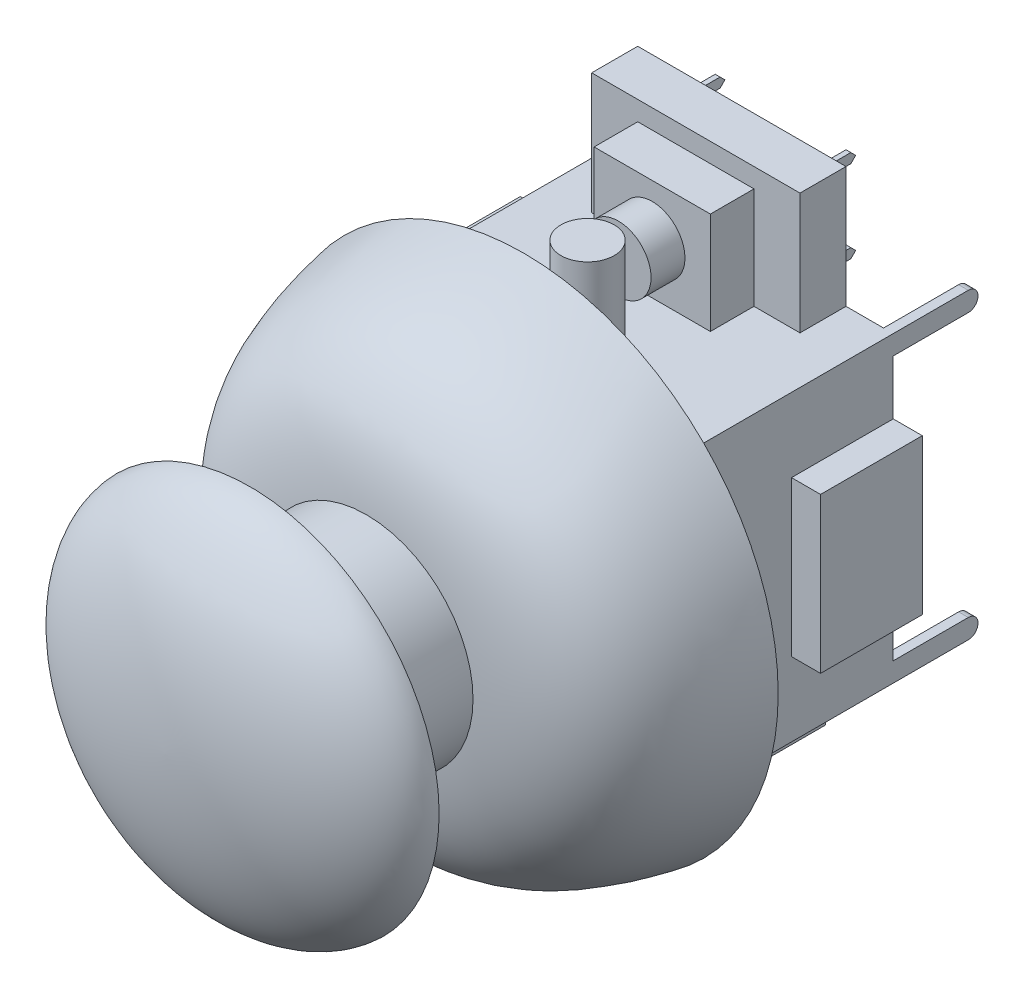
SolidWorks part; units mm, degrees
ref_plane "Front Plane" through (0, 0, 0) normal (0, 0, 1) x (1, 0, 0)
ref_plane "Top Plane" through (0, 0, 0) normal (0, 1, 0) x (1, 0, 0)
ref_plane "Right Plane" through (0, 0, 0) normal (1, 0, 0) x (0, 0, -1)
sketch "Sketch1" plane through (0, 0, 0) normal (0, 0, 1) x (1, 0, 0)
  line L1 (0, 0) -> (15.875, 0)
  line L2 (0, 0) -> (0, 15.875)
  line L3 (0, 15.875) -> (15.875, 15.875)
  line L4 (15.875, 0) -> (15.875, 15.875)
  dimension "D1" = 15.875
extrude "Boss-Extrude1" add sketch "Sketch1" along normal blind 11.938
sketch "Sketch2" plane through (0, 0, 0) normal (0, 0, -1) x (-1, 0, 0)
  line L0 (-7.9375, 15.875) -> (-7.9375, 24.013) construction
  line L1 (-15.875, 15.875) -> (0, 15.875) construction
  line L3 (-13.3985, 15.875) -> (-2.4765, 15.875)
  line L4 (-13.3985, 15.875) -> (-13.3985, 22.225)
  line L5 (-13.3985, 22.225) -> (-2.4765, 22.225)
  line L6 (-2.4765, 15.875) -> (-2.4765, 22.225)
  point P8 (-7.9375, 22.225)
  dimension "D1" = 10.922
  dimension "D2" = 6.35
extrude "Boss-Extrude2" add sketch "Sketch2" against normal blind 2.413
sketch "Sketch3" plane through (15.875, 0, 0) normal (1, 0, 0) x (0, 0, -1)
  line L0 (0, 0) -> (0, 15.875) construction
  line L1 (0, 3.8735) -> (-5.334, 3.8735)
  line L2 (0, 3.8735) -> (0, 12.0015)
  line L3 (0, 12.0015) -> (-5.334, 12.0015)
  line L4 (-5.334, 3.8735) -> (-5.334, 12.0015)
  line L5 (-11.938, 7.9375) -> (0, 7.9375) construction
  line L6 (-11.938, 0) -> (-11.938, 15.875) construction
  point P10 (-5.334, 7.9375)
  dimension "D1" = 8.128
  dimension "D2" = 5.334
extrude "Boss-Extrude3" add sketch "Sketch3" along normal blind 1.524
sketch "Sketch4" plane through (0, 0, 2.413) normal (0, 0, 1) x (1, 0, 0)
  line L0 (7.9375, 22.225) -> (7.9375, 15.875) construction
  line L1 (2.4765, 22.225) -> (13.3985, 22.225) construction
  line L2 (13.3985, 15.875) -> (2.4765, 15.875) construction
  line L3 (15.875, 15.875) -> (0, 15.875) construction
  line L4 (4.8895, 15.875) -> (10.9855, 15.875)
  line L5 (4.8895, 15.875) -> (4.8895, 21.209)
  line L6 (4.8895, 21.209) -> (10.9855, 21.209)
  line L7 (10.9855, 15.875) -> (10.9855, 21.209)
  point P12 (7.9375, 21.209)
  dimension "D1" = 6.096
  dimension "D2" = 5.334
extrude "Boss-Extrude4" add sketch "Sketch4" along normal blind 2.286
sketch "Sketch5" plane through (0, 0, 4.699) normal (0, 0, 1) x (1, 0, 0)
  line L0 (7.9375, 21.209) -> (7.9375, 15.875) construction
  line L1 (10.9855, 21.209) -> (4.8895, 21.209) construction
  line L2 (4.8895, 15.875) -> (10.9855, 15.875) construction
  line L3 (4.8895, 18.542) -> (10.9855, 18.542) construction
  line L4 (4.8895, 21.209) -> (4.8895, 15.875) construction
  line L5 (10.9855, 15.875) -> (10.9855, 21.209) construction
  circle A0 centre (7.9375, 18.542) radius 1.7145
  dimension "D1" = 3.429
extrude "Boss-Extrude5" add sketch "Sketch5" along normal blind 1.778
sketch "Sketch6" plane through (0, 15.875, 0) normal (0, 1, 0) x (1, 0, 0)
  line L0 (7.9375, -11.938) -> (7.9375, -4.699) construction
  line L1 (15.875, -11.938) -> (0, -11.938) construction
  line L2 (10.9855, -4.699) -> (4.8895, -4.699) construction
  circle A0 centre (7.9375, -8.0902) radius 1.397
  dimension "D1" = 2.794
extrude "Boss-Extrude6" add sketch "Sketch6" along normal blind 4.318
sketch "Sketch7" plane through (0, 0, 0) normal (0, -1, 0) x (1, 0, 0)
  line L0 (7.9375, 11.938) -> (7.9375, 0) construction
  line L1 (0, 11.938) -> (15.875, 11.938) construction
  line L2 (0, 0) -> (15.875, 0) construction
  line L4 (3.048, 11.938) -> (12.827, 11.938)
  line L5 (3.048, 11.938) -> (3.048, 0.508)
  line L6 (3.048, 0.508) -> (12.827, 0.508)
  line L7 (12.827, 11.938) -> (12.827, 0.508)
  point P10 (7.9375, 0.508)
  dimension "D1" = 9.779
  dimension "D2" = 11.43
extrude "Boss-Extrude7" add sketch "Sketch7" along normal blind 3.175 separate body
sketch "Sketch8" plane through (0, 0, 0) normal (-1, 0, 0) x (0, 0, 1)
  line L0 (11.938, 7.9375) -> (0, 7.9375) construction
  line L1 (11.938, 15.875) -> (11.938, 0) construction
  line L2 (0, 15.875) -> (0, 0) construction
  line L4 (11.938, 12.827) -> (0.508, 12.827)
  line L5 (11.938, 12.827) -> (11.938, 3.048)
  line L6 (11.938, 3.048) -> (0.508, 3.048)
  line L7 (0.508, 12.827) -> (0.508, 3.048)
  point P10 (0.508, 7.9375)
  dimension "D1" = 9.779
  dimension "D2" = 11.43
extrude "Boss-Extrude8" add sketch "Sketch8" along normal blind 3.175 separate body
sketch "Sketch9" plane through (-3.175, 0, 0) normal (-1, 0, 0) x (0, 0, 1)
  line L0 (11.938, 7.9375) -> (0.508, 7.9375) construction
  line L1 (11.938, 3.048) -> (11.938, 12.827) construction
  line L2 (0.508, 12.827) -> (0.508, 3.048) construction
  line L3 (7.62, 12.4456) -> (7.62, 10.8887)
  line L4 (6.096, 12.4456) -> (6.096, 10.8887)
  line L5 (11.3661, 7.1755) -> (9.8092, 7.1755)
  line L6 (11.3661, 8.6995) -> (9.8092, 8.6995)
  line L7 (6.096, 3.4294) -> (6.096, 4.9863)
  line L8 (7.62, 3.4294) -> (7.62, 4.9863)
  line L10 (2.3499, 7.1755) -> (3.9068, 7.1755)
  line L14 (2.3499, 8.6995) -> (3.9068, 8.6995)
  arc A0 (2.3499, 7.1755) -> (6.096, 3.4294) centre (6.858, 7.9375) ccw
  arc A1 (3.9068, 7.1755) -> (6.096, 4.9863) centre (6.858, 7.9375) ccw
  circle A2 centre (6.858, 7.9375) radius 2.413
  circle A3 centre (6.858, 7.9375) radius 1.8415
  arc A4 (6.096, 12.4456) -> (2.3499, 8.6995) centre (6.858, 7.9375) ccw
  arc A5 (6.096, 10.8887) -> (3.9068, 8.6995) centre (6.858, 7.9375) ccw
  arc A6 (9.8092, 8.6995) -> (7.62, 10.8887) centre (6.858, 7.9375) ccw
  arc A7 (11.3661, 8.6995) -> (7.62, 12.4456) centre (6.858, 7.9375) ccw
  arc A8 (7.62, 4.9863) -> (9.8092, 7.1755) centre (6.858, 7.9375) ccw
  arc A9 (7.62, 3.4294) -> (11.3661, 7.1755) centre (6.858, 7.9375) ccw
  point P25 (6.858, 7.9375)
  dimension "D2" = 9.144
  dimension "D3" = 6.096
  dimension "D4" = 4.826
  dimension "D5" = 3.683
  dimension "D1" = 5.08
  dimension "D8" = 1.524
  dimension "D6" = 4
extrude "Cut-Extrude1" cut sketch "Sketch9" against normal blind 0.508
sketch "Sketch10" plane through (0, -3.175, 0) normal (0, -1, 0) x (1, 0, 0)
  line L0 (7.9375, 11.938) -> (7.9375, 0.508) construction
  line L1 (3.4294, 7.62) -> (4.9863, 7.62)
  line L2 (3.4294, 6.096) -> (4.9863, 6.096)
  line L3 (8.6995, 11.3661) -> (8.6995, 9.8092)
  line L4 (7.1755, 11.3661) -> (7.1755, 9.8092)
  line L5 (12.4456, 6.096) -> (10.8887, 6.096)
  line L6 (12.4456, 7.62) -> (10.8887, 7.62)
  line L7 (8.6995, 2.3499) -> (8.6995, 3.9068)
  line L8 (7.1755, 2.3499) -> (7.1755, 3.9068)
  line L9 (3.048, 11.938) -> (12.827, 11.938) construction
  arc A0 (8.6995, 2.3499) -> (12.4456, 6.096) centre (7.9375, 6.858) ccw
  arc A1 (8.6995, 3.9068) -> (10.8887, 6.096) centre (7.9375, 6.858) ccw
  circle A2 centre (7.9375, 6.858) radius 2.413
  circle A3 centre (7.9375, 6.858) radius 1.8415
  arc A4 (3.4294, 6.096) -> (7.1755, 2.3499) centre (7.9375, 6.858) ccw
  arc A5 (4.9863, 6.096) -> (7.1755, 3.9068) centre (7.9375, 6.858) ccw
  arc A6 (7.1755, 9.8092) -> (4.9863, 7.62) centre (7.9375, 6.858) ccw
  arc A7 (7.1755, 11.3661) -> (3.4294, 7.62) centre (7.9375, 6.858) ccw
  arc A8 (10.8887, 7.62) -> (8.6995, 9.8092) centre (7.9375, 6.858) ccw
  arc A9 (12.4456, 7.62) -> (8.6995, 11.3661) centre (7.9375, 6.858) ccw
  point P18 (7.9375, 6.858)
  dimension "D1" = 4.826
extrude "Cut-Extrude2" cut sketch "Sketch10" against normal blind 0.508
ref_plane "Plane3" through (7.9375, 7.9375, 0) normal (-0.7071, -0.7071, 0) x (-0.7071, 0.7071, 0)
ref_plane "Plane4" through (0, 0, 0) normal (0.7071, -0.7071, 0) x (-0.7071, -0.7071, 0)
ref_axis "Axis2" through (7.9375, 7.9375, -0.5969) along (0, 0, 1)
sketch "Sketch11" plane through (7.9375, 7.9375, 0) normal (-0.7071, -0.7071, 0) x (-0.7071, 0.7071, 0)
  line L0 (0, -11.938) -> (0, -30.226)
  line L1 (0, 6.5659) -> (0, -6.5659) construction
  line L2 (11.2253, -11.938) -> (0, -11.938) construction
  line L3 (-18.1706, -11.43) -> (26.2656, -11.43) construction
  line L4 (11.2253, 0) -> (0, 0) construction
  line L5 (13.335, -11.43) -> (13.335, -19.685) construction
  line L6 (13.335, -19.685) -> (0, -19.685) construction
  line L7 (3.1115, -11.938) -> (3.1115, -15.1787)
  line L8 (5.588, -19.685) -> (5.588, -24.511)
  line L9 (3.1115, -15.1787) -> (5.08, -19.2254)
  line L10 (5.08, -19.2254) -> (5.08, -24.511) construction
  line L11 (13.335, -11.43) -> (12.8178, -11.43)
  line L12 (0, -30.226) -> (9.906, -30.226) construction
  line L13 (9.906, -24.511) -> (9.906, -25.781) construction
  line L14 (9.906, -24.511) -> (5.588, -24.511) construction
  line L15 (5.588, -24.511) -> (9.906, -25.781)
  line L16 (3.1115, -11.938) -> (0, -11.938)
  spline S0 degree 3 poles (5.588, -19.685) (10.7036, -19.1717) (12.3371, -16.6782) (13.335, -11.43) knots 0 0 0 0 1 1 1 1
  spline S1 degree 1 poles (5.08, -19.2254) (12.8359, -11.3351) knots 0 0 1 1 construction
  spline S2 degree 3 poles (5.08, -19.2254) (5.3999, -19.1933) (6.0617, -19.1294) (7.2028, -18.9354) (8.4381, -18.5762) (9.6141, -17.9582) (10.5555, -17.1454) (11.3172, -16.1066) (11.9356, -14.8112) (12.3533, -13.4974) (12.64, -12.3157) (12.7747, -11.6573) (12.8359, -11.3351) knots -0.029797 -0.029797 -0.029797 -0.029797 0.034566 0.098928 0.227653 0.356377 0.485102 0.613826 0.742551 0.871275 0.935638 1 1 1 1 only from (5.08, -19.2254) to (12.8178, -11.43)
  spline S3 degree 3 poles (9.906, -25.781) (9.7517, -27.8565) (6.0405, -30.162) (0, -30.226) knots 0 0 0 0 1 1 1 1
  dimension "D1" = 11.43
  dimension "D2" = 13.335
  dimension "D3" = 18.796
  dimension "D4" = 8.255
  dimension "D5" = 3.1115
  dimension "D6" = 5.588
  dimension "D7" = 4.826
  dimension "D9" = 9.906
  dimension "D10" = 1.27
  dimension "D8" = 0.508
revolve "Revolve1" add sketch "Sketch11" angle 360 about axis through (7.9375, 7.9375, -0.5969) along (0, 0, 1)
sketch "Sketch12" plane through (0, 0, 0) normal (0, -1, 0) x (1, 0, 0)
  line L0 (0, 0) -> (0, -4.445)
  line L1 (15.875, 11.938) -> (15.875, 0) construction
  line L2 (0, 0) -> (15.875, 0) construction
  line L3 (15.367, 0) -> (15.367, -4.445)
  dimension "D1" = 4.445
  dimension "D2" = 0.508
extrude "Extrude-Thin1" add sketch "Sketch12" against normal blind 1.016 thin thin type one direction reverse wall 0.508
sketch "Sketch13" plane through (0, 15.875, 0) normal (0, 1, 0) x (1, 0, 0)
  line L0 (0, 0) -> (0, 4.445)
  line L2 (15.367, 0) -> (15.367, 4.445)
extrude "Extrude-Thin2" add sketch "Sketch13" against normal blind 1.016 thin thin type one direction wall 0.508
fillet "Fillet1" radius 0.508 8 edges at (0.254, 1.016, -4.445) (0.254, 15.875, -4.445) (15.621, 15.875, -4.445) (15.621, 1.016, -4.445) (15.621, 0, -4.445) (15.621, 14.859, -4.445) (0.254, 14.859, -4.445) (0.254, 0, -4.445)
ref_plane "Plane5" through (0, -1.5875, 0) normal (0, -1, 0) x (-1, 0, 0)
ref_plane "Plane6" through (-1.5875, 0, 0) normal (-1, 0, 0) x (0, 0, 1)
sketch "Sketch14" plane through (0, -1.5875, 0) normal (0, -1, 0) x (-1, 0, 0)
  line L0 (-7.9375, -0.508) -> (-7.9375, 4.2984) construction
  line L1 (-3.048, -0.508) -> (-12.827, -0.508) construction
  line L2 (-5.3975, -0.508) -> (-5.3975, 4.2984) construction
  line L3 (-10.4775, -0.508) -> (-10.4775, 4.2984) construction
  line L4 (-10.0965, -0.508) -> (-10.0965, 3.6973)
  line L5 (-7.5565, -0.508) -> (-7.5565, 3.6973)
  line L6 (-5.0165, -0.508) -> (-5.0165, 3.6973)
  line L7 (-10.8585, -0.508) -> (-10.8585, 3.6973)
  line L8 (-8.3185, -0.508) -> (-8.3185, 3.6973)
  line L9 (-5.7785, -0.508) -> (-5.7785, 3.6973)
  line L10 (-10.4775, 4.2984) -> (-10.8585, 3.6973)
  line L11 (-7.9375, 4.2984) -> (-8.3185, 3.6973)
  line L12 (-10.0965, 3.6973) -> (-10.4775, 4.2984)
  line L13 (-7.5565, 3.6973) -> (-7.9375, 4.2984)
  line L14 (-5.3975, 4.2984) -> (-5.7785, 3.6973)
  line L15 (-5.0165, 3.6973) -> (-5.3975, 4.2984)
  line L16 (-10.8585, -0.508) -> (-10.8585, 4.2984) construction
  line L17 (-10.0965, -0.508) -> (-10.0965, 4.2984) construction
  line L18 (-8.3185, -0.508) -> (-8.3185, 4.2984) construction
  line L19 (-7.5565, -0.508) -> (-7.5565, 4.2984) construction
  line L20 (-5.7785, -0.508) -> (-5.7785, 4.2984) construction
  line L21 (-5.0165, -0.508) -> (-5.0165, 4.2984) construction
  line L22 (-10.8585, -0.508) -> (-10.0965, -0.508)
  line L23 (-8.3185, -0.508) -> (-7.5565, -0.508)
  line L24 (-5.7785, -0.508) -> (-5.0165, -0.508)
  dimension "D1" = 2.54
  dimension "D2" = 2.54
  dimension "D3" = 0.381
  dimension "D4" = 0.381
extrude "Boss-Extrude9" add sketch "Sketch14" along normal mid plane 0.508
sketch "Sketch15" plane through (-1.5875, 0, 0) normal (-1, 0, 0) x (0, 0, 1)
  line L0 (0.508, 7.9375) -> (-4.2984, 7.9375) construction
  line L1 (0.508, 8.3185) -> (-3.6973, 8.3185)
  line L2 (0.508, 7.5565) -> (-3.6973, 7.5565)
  line L3 (-4.2984, 7.9375) -> (-3.6973, 7.5565)
  line L4 (-3.6973, 8.3185) -> (-4.2984, 7.9375)
  line L5 (0.508, 7.5565) -> (0.508, 8.3185)
  line L6 (0.508, 5.7785) -> (-3.6973, 5.7785)
  line L8 (0.508, 5.0165) -> (-3.6973, 5.0165)
  line L9 (-4.2984, 5.3975) -> (-3.6973, 5.0165)
  line L10 (-3.6973, 5.7785) -> (-4.2984, 5.3975)
  line L11 (0.508, 5.0165) -> (0.508, 5.7785)
  line L12 (0.508, 5.3975) -> (-4.2984, 5.3975) construction
  line L19 (0.508, 10.8585) -> (-3.6973, 10.8585)
  line L20 (0.508, 10.0965) -> (-3.6973, 10.0965)
  line L21 (-4.2984, 10.4775) -> (-3.6973, 10.0965)
  line L22 (-3.6973, 10.8585) -> (-4.2984, 10.4775)
  line L23 (0.508, 10.0965) -> (0.508, 10.8585)
  line L24 (0.508, 10.4775) -> (-4.2984, 10.4775) construction
  line L25 (0.508, 7.9375) -> (-4.2984, 7.9375) construction
  line L26 (0.508, 7.5565) -> (0.508, 8.3185) [skipped]
  line L27 (0.508, 7.5565) -> (-3.6973, 7.5565) [skipped]
  line L28 (-4.2984, 7.9375) -> (-3.6973, 7.5565) [skipped]
  line L29 (-3.6973, 8.3185) -> (-4.2984, 7.9375) [skipped]
  line L30 (0.508, 8.3185) -> (-3.6973, 8.3185) [skipped]
  dimension "D1" = 2
  dimension "D2" = 2
extrude "Boss-Extrude10" add sketch "Sketch15" along normal mid plane 0.508
sketch "Sketch16" plane through (0, 0, 0) normal (0, 0, -1) x (-1, 0, 0)
  line L0 (-13.3985, 22.225) -> (-13.3985, 15.875) construction
  line L1 (-11.3665, 20.701) -> (-11.1125, 20.701)
  line L2 (-11.3665, 20.701) -> (-11.3665, 20.193)
  line L3 (-11.3665, 20.193) -> (-11.1125, 20.193)
  line L4 (-11.1125, 20.701) -> (-11.1125, 20.193)
  line L5 (-2.4765, 22.225) -> (-13.3985, 22.225) construction
  line L6 (-4.5085, 20.701) -> (-4.2545, 20.701)
  line L7 (-4.5085, 20.701) -> (-4.5085, 20.193)
  line L8 (-4.5085, 20.193) -> (-4.2545, 20.193)
  line L9 (-4.2545, 20.701) -> (-4.2545, 20.193)
  line L10 (-4.5085, 16.383) -> (-4.2545, 16.383)
  line L11 (-4.5085, 16.383) -> (-4.5085, 15.875)
  line L12 (-4.5085, 15.875) -> (-4.2545, 15.875)
  line L13 (-4.2545, 16.383) -> (-4.2545, 15.875)
  line L14 (-11.3665, 16.383) -> (-11.1125, 16.383)
  line L15 (-11.3665, 16.383) -> (-11.3665, 15.875)
  line L16 (-11.3665, 15.875) -> (-11.1125, 15.875)
  line L17 (-11.1125, 16.383) -> (-11.1125, 15.875)
  dimension "D1" = 2.032
  dimension "D2" = 1.524
  dimension "D3" = 0.254
  dimension "D4" = 0.508
  dimension "D5" = 2
  dimension "D6" = 2
extrude "Boss-Extrude11" add sketch "Sketch16" along normal blind 2.54
chamfer "Chamfer1" distance 0.254 angle 45 8 edges at (11.2395, 15.875, -2.54) (11.2395, 16.383, -2.54) (4.3815, 15.875, -2.54) (4.3815, 16.383, -2.54) (4.3815, 20.193, -2.54) (4.3815, 20.701, -2.54) (11.2395, 20.193, -2.54) (11.2395, 20.701, -2.54)
